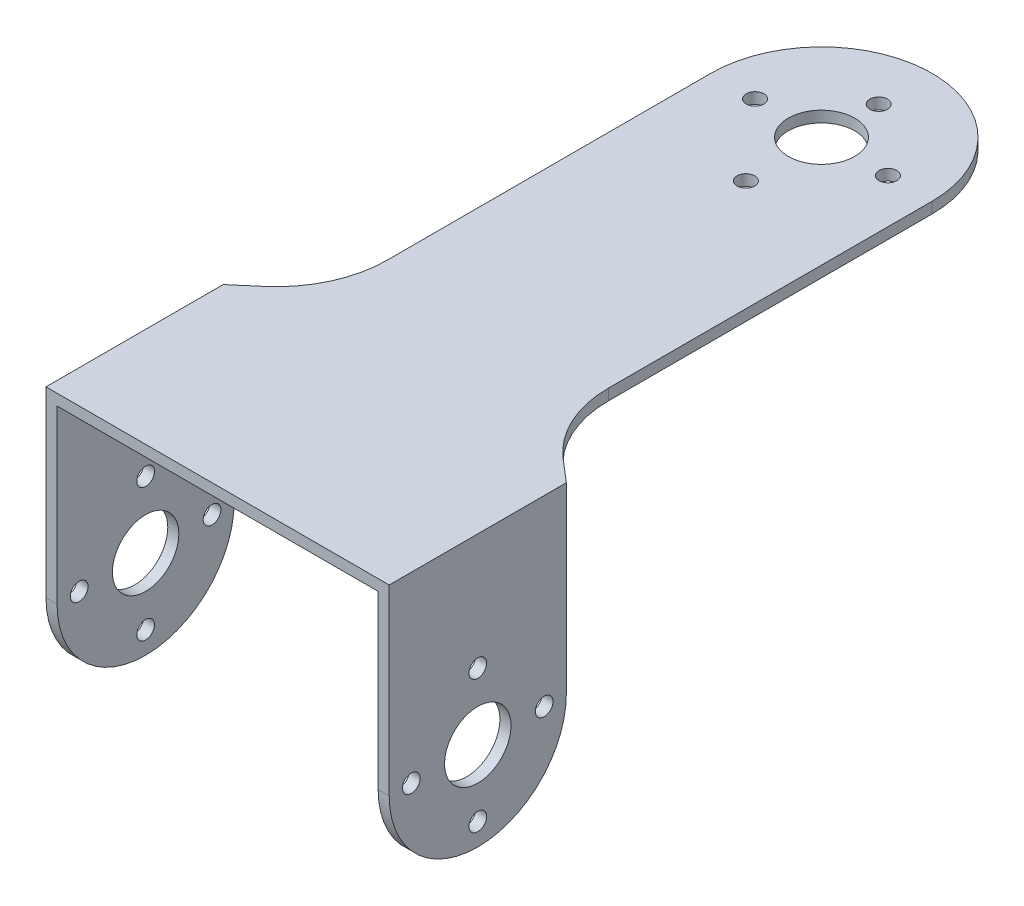
SolidWorks part; units mm, degrees
ref_plane "Front Plane" through (0, 0, 0) normal (0, 0, 1) x (1, 0, 0)
ref_plane "Top Plane" through (0, 0, 0) normal (0, 1, 0) x (1, 0, 0)
ref_plane "Right Plane" through (0, 0, 0) normal (1, 0, 0) x (0, 0, -1)
sketch "Sketch1" plane through (0, 0, 0) normal (1, 0, 0) x (0, 0, -1)
  line L0 (27.5206, 38.7756) -> (27.5206, 55.2756)
  line L1 (35.5206, 38.7756) -> (35.5206, 32.7756) construction
  line L6 (35.5206, 38.7756) -> (41.5159, 38.7756) construction
  line L7 (35.5206, 38.7756) -> (35.5206, 44.7756) construction
  line L8 (35.5206, 38.7756) -> (29.5159, 38.7756) construction
  line L9 (27.5206, 55.2756) -> (43.5206, 55.2756)
  line L10 (43.5206, 55.2756) -> (43.5206, 38.7756)
  arc A0 (27.5206, 38.7756) -> (43.5206, 38.7756) centre (35.5206, 38.7756) ccw
  circle A1 centre (35.5206, 44.7756) radius 0.8
  circle A2 centre (41.5159, 38.7756) radius 0.8
  circle A3 centre (35.5206, 32.7756) radius 0.8
  circle A4 centre (29.5159, 38.7756) radius 0.8
  circle A5 centre (35.5206, 38.7756) radius 3
  point P8 (35.5206, 38.7756)
extrude "Boss-Extrude1" add sketch "Sketch1" along normal blind 31
sketch "Sketch4" plane through (0, 55.2756, 0) normal (0, 1, 0) x (1, 0, 0)
  line L0 (0, 43.5206) -> (31, 43.5206)
  line L6 (5.5, 82.0661) -> (5.5, 52.8347)
  line L7 (2.0088, 45.2429) -> (0, 43.5206)
  line L8 (25.5, 82.0661) -> (25.5, 52.8347)
  line L9 (28.9912, 45.2429) -> (31, 43.5206)
  arc A2 (25.5, 82.0661) -> (5.5, 82.0661) centre (15.5, 82.0661) ccw
  arc A4 (25.5, 52.8347) -> (28.9912, 45.2429) centre (35.5, 52.8347) ccw
  arc A5 (5.5, 52.8347) -> (2.0088, 45.2429) centre (-4.5, 52.8347) cw
  dimension "D1" = 10
extrude "Boss-Extrude2" add sketch "Sketch4" against normal blind 1
sketch "Sketch5" plane through (0, 54.2756, 0) normal (0, -1, 0) x (1, 0, 0)
  circle A0 centre (15.5, -82.0661) radius 8
  circle A1 centre (9.5, -82.0661) radius 0.8
  circle A2 centre (15.5, -75.2361) radius 0.8
  circle A3 centre (21.5, -82.0661) radius 0.8
  circle A4 centre (15.5, -87.2361) radius 0.8
  circle A5 centre (15.5, -82.0661) radius 3
extrude "Cut-Extrude3" cut sketch "Sketch5" against normal blind 1 contours A3 | A4 | A1 | A2
extrude "Cut-Extrude4" cut sketch "Sketch5<3>" against normal blind 1 contours A5
sketch "Sketch5<3>" plane through (0, 54.2756, 0) normal (0, -1, 0) x (1, 0, 0) same geometry as "Sketch5"
sketch "Sketch6" plane through (0, 55.2756, 0) normal (0, 1, 0) x (1, 0, 0)
  line L0 (15.5, 43.5206) -> (15.5, 43.4947)
  line L1 (0, 43.5206) -> (31, 43.5206) construction
  line L2 (31, 27.5206) -> (0, 27.5206) construction
  line L3 (0.9992, 43.4947) -> (0.9992, 44.172)
  line L4 (0.9992, 44.172) -> (30.0008, 44.172)
  line L6 (0.9992, 27.5466) -> (0.9992, 43.4947)
  line L7 (30.0008, 27.5466) -> (30.0008, 43.4947)
  line L9 (0.9992, 27.5466) -> (15.5, 35.5206) construction
  line L10 (15.5, 35.5206) -> (0.9992, 43.4947) construction
  line L11 (15.5, 27.5466) -> (15.5, 27.5206)
  line L12 (30.0008, 44.172) -> (30.0008, 43.4947)
  line L13 (0.9992, 27.5466) -> (0.9992, 27.029)
  line L14 (0.9992, 27.029) -> (30.0008, 27.029)
  line L15 (30.0008, 27.029) -> (30.0008, 27.5466)
extrude "Cut-Extrude5" cut sketch "Sketch6" against normal through all from offset 1 contours L6 L7 region at (15.5, 55.2756, -35.6005) offset against normal yes
sketch "Sketch7" plane through (0, 0, 0) normal (-1, 0, 0) x (0, 0, 1)
  point P0 (-35.5206, 38.7756)
sketch "Sketch8" plane through (0, 54.2756, 0) normal (0, -1, 0) x (1, 0, 0)
  circle A0 centre (15.5, -82.0661) radius 25
  circle A1 centre (15.5, -82.0661) radius 3
  circle A2 centre (15.5, -75.2361) radius 0.8
  circle A3 centre (21.5, -82.0661) radius 0.8
  circle A4 centre (15.5, -87.2361) radius 0.8
  circle A5 centre (9.5, -82.0661) radius 0.8
